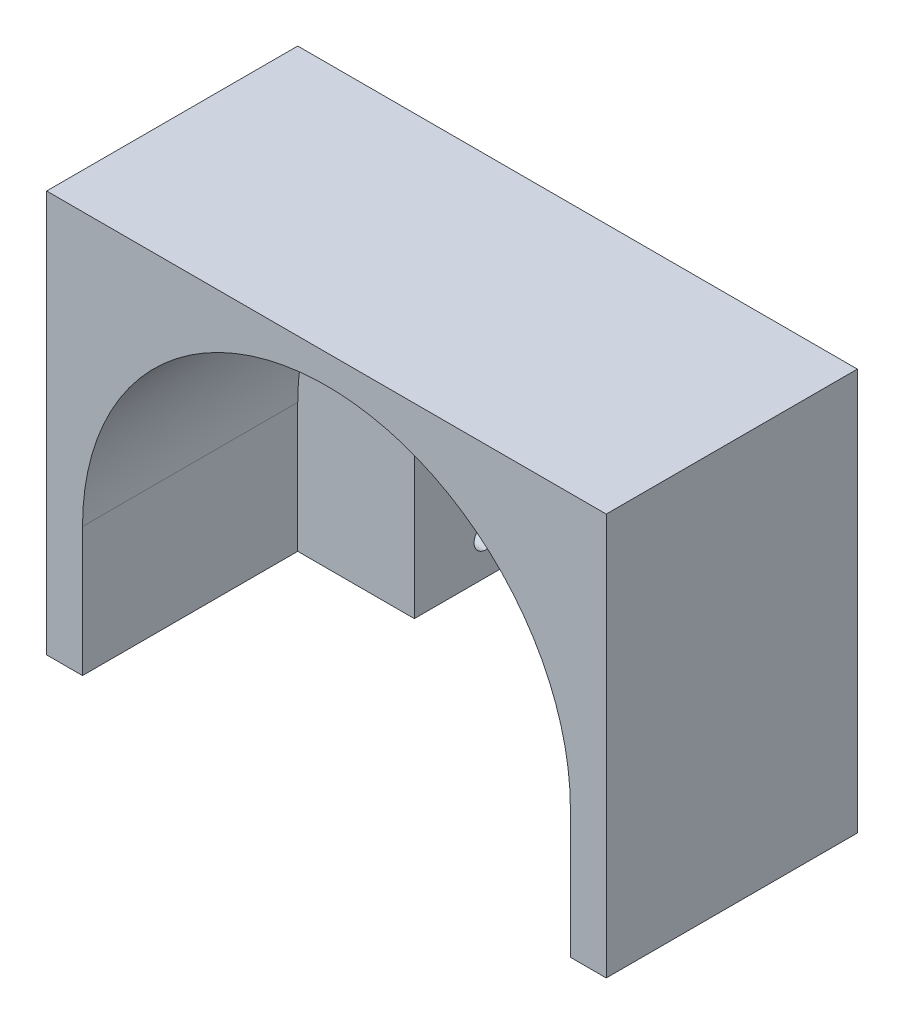
SolidWorks part; units mm, degrees
ref_plane "Plan de face" through (0, 0, 0) normal (0, 0, 1) x (1, 0, 0)
ref_plane "Plan de dessus" through (0, 0, 0) normal (0, 1, 0) x (1, 0, 0)
ref_plane "Plan de droite" through (0, 0, 0) normal (1, 0, 0) x (0, 0, -1)
ref_plane "Plan2" through (0, -10, 0) normal (0, 1, 0) x (1, 0, 0)
sketch "Esquisse3" plane through (0, 0, 0) normal (0, 0, 1) x (1, 0, 0)
  line L1 (-39, 28) -> (39, 28)
  line L2 (-39, 28) -> (-39, -28)
  line L3 (-39, -28) -> (39, -28)
  line L4 (39, 28) -> (39, -28)
  point P4 (0, 28)
  point P5 (-39, 0)
  point P8 (39, 0)
  point P9 (0, -28)
  dimension "D1" = 78
  dimension "D2" = 56
extrude "Boss.-Extru.2" add sketch "Esquisse3" along normal blind 45
sketch "Esquisse4" plane through (0, 0, 45) normal (0, 0, 1) x (1, 0, 0)
  line L2 (39, 28) -> (-39, 28) construction
  line L3 (55, -10) -> (-55, -10) construction
  circle A0 centre (0, -10) radius 34
  point P2 (0, 28)
  dimension "D1" = 68
extrude "Enlèv. mat.-Extru.1" cut sketch "Esquisse4" against normal blind 30
sketch "Esquisse5" plane through (0, 0, 0) normal (0, 0, -1) x (-1, 0, 0)
  line L0 (39, -28) -> (-39, -28) construction
  line L1 (-17.75, 7) -> (17.75, 7)
  line L2 (-17.75, 7) -> (-17.75, -28)
  line L3 (-17.75, -28) -> (17.75, -28)
  line L4 (17.75, 7) -> (17.75, -28)
  point P6 (0, -28)
  dimension "D1" = 35.5
  dimension "D2" = 35
extrude "Enlèv. mat.-Extru.2" cut sketch "Esquisse5" against normal up to surface (15 mm away) up to face at (0, -2, 15)
sketch "Esquisse8" plane through (0, 0, 0) normal (0, 0, -1) x (-1, 0, 0)
  line L0 (-22.75, -28) -> (-22.75, 12)
  line L1 (-17.75, -28) -> (-39, -28) construction
  line L2 (-22.75, 12) -> (22.75, 12)
  line L3 (22.75, 12) -> (22.75, -28)
  line L4 (39, -28) -> (17.75, -28) construction
  line L5 (22.75, -28) -> (39, -28)
  line L6 (39, -28) -> (39, 28)
  line L7 (39, 28) -> (-39, 28)
  line L8 (-39, 28) -> (-39, -28)
  line L9 (-39, -28) -> (-22.75, -28)
  line L10 (17.75, 7) -> (-17.75, 7) construction
  line L11 (-17.75, 7) -> (-17.75, -28) construction
  line L12 (17.75, -28) -> (17.75, 7) construction
  dimension "D1" = 5
  dimension "D2" = 5
  dimension "D3" = 5
extrude "Enlèv. mat.-Extru.5" cut sketch "Esquisse8" against normal blind 10
sketch "Esquisse12" plane through (0, 0, 45) normal (0, 0, 1) x (1, 0, 0)
  line L0 (-39, -28) -> (-28.8444, -28) construction
  line L1 (-34, -28) -> (34, -28)
  line L2 (-34, -28) -> (-34, -10)
  line L3 (-34, -10) -> (34, -10)
  line L4 (34, -28) -> (34, -10)
  line L5 (55, -10) -> (-55, -10) construction
  arc A0 (28.8444, -28) -> (-28.8444, -28) centre (0, -10) ccw construction
extrude "Enlèv. mat.-Extru.6" cut sketch "Esquisse12" against normal up to surface (30 mm away) up to face at (0, -7.6667, 15)
sketch "Esquisse13" plane through (-22.75, 0, 0) normal (-1, 0, 0) x (0, 0, 1)
  line L0 (0, 12) -> (0, -28) construction
  line L1 (10, -28) -> (0, -28) construction
  circle A0 centre (5, -23) radius 1.6715
  dimension "D1" = 5
  dimension "D2" = 5
extrude "Enlèv. mat.-Extru.7" cut sketch "Esquisse13" against normal through all
sketch "Esquisse15" plane through (-22.75, 0, 0) normal (-1, 0, 0) x (0, 0, 1)
  line L0 (10, 12) -> (0, 12) construction
  line L1 (0, 12) -> (0, -28) construction
  circle A0 centre (5, 2) radius 1.5
  dimension "D1" = 3
  dimension "D2" = 10
  dimension "D3" = 5
extrude "Enlèv. mat.-Extru.8" cut sketch "Esquisse15" against normal through all
sketch "Esquisse16" plane through (0, 0, 15) normal (0, 0, 1) x (1, 0, 0)
  line L0 (-17.75, -28) -> (-17.75, 7) construction
  line L1 (-21.75, 3) -> (21.75, 3)
  line L2 (-21.75, 3) -> (-21.75, 11)
  line L3 (-21.75, 11) -> (21.75, 11)
  line L4 (21.75, 3) -> (21.75, 11)
  line L5 (17.75, 7) -> (17.75, -28) construction
  line L6 (-17.75, 7) -> (17.75, 7) construction
  dimension "D1" = 4
  dimension "D2" = 4
  dimension "D3" = 4
  dimension "D4" = 4
extrude "Enlèv. mat.-Extru.9" cut sketch "Esquisse16" against normal blind 3
sketch "Esquisse17" plane through (0, 12, 0) normal (0, 1, 0) x (1, 0, 0)
  line L0 (-22.75, -10) -> (-22.75, 0) construction
  line L1 (22.75, 0) -> (-22.75, 0) construction
  circle A0 centre (-12.75, -5) radius 1.5
  dimension "D1" = 3
  dimension "D2" = 10
  dimension "D3" = 5
extrude "Enlèv. mat.-Extru.10" cut sketch "Esquisse17" against normal through all
sketch "Esquisse18" plane through (0, 12, 0) normal (0, 1, 0) x (1, 0, 0)
  line L0 (22.75, -10) -> (22.75, 0) construction
  circle A0 centre (12.75, -5) radius 1.5
  dimension "D1" = 3
  dimension "D2" = 5
  dimension "D3" = 10
extrude "Enlèv. mat.-Extru.11" cut sketch "Esquisse18" against normal through all
